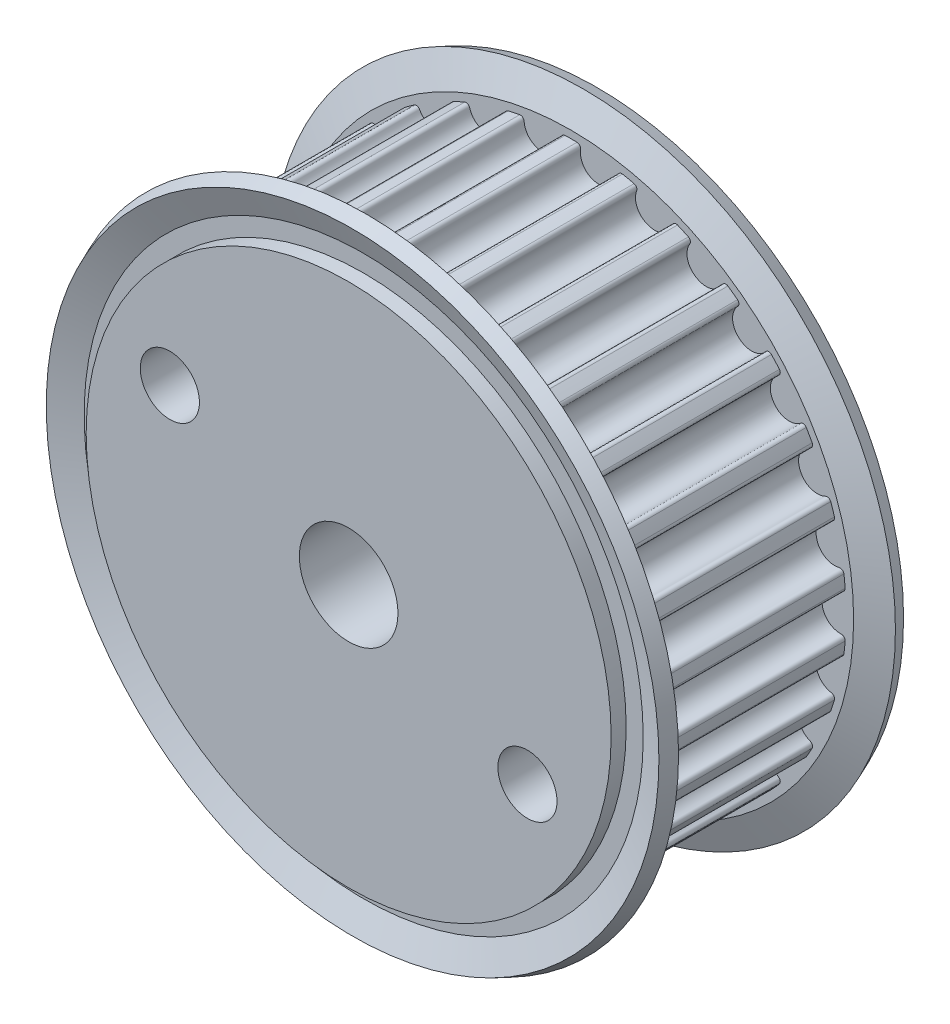
SolidWorks part; units mm, degrees
material "6061 合金"
ref_plane "前视基准面" through (0, 0, 0) normal (0, 0, 1) x (1, 0, 0)
ref_plane "上视基准面" through (0, 0, 0) normal (0, 1, 0) x (1, 0, 0)
ref_plane "右视基准面" through (0, 0, 0) normal (1, 0, 0) x (0, 0, -1)
ref_axis "基准轴1" through (0, 0, 55) along (0, 0, -1)
sketch "SketchRevolveGearBelt01" plane through (0, 0, 0) normal (1, 0, 0) x (0, 0, -1)
  line L0 (0, 0) -> (1, 0) construction
  line L1 (6.4008, 0) -> (6.4008, 13.3069)
  line L2 (6.4008, 13.3069) -> (5.6388, 13.3069)
  line L3 (5.6388, 13.3069) -> (5.6388, 14.1713)
  line L4 (5.6388, 14.1713) -> (6.2015, 15.5299)
  line L5 (6.2015, 15.5299) -> (5.4975, 15.8215)
  line L6 (5.4975, 15.8215) -> (4.8768, 14.3229)
  line L7 (4.8768, 14.3229) -> (4.8768, 13.9419)
  line L8 (4.8768, 13.9419) -> (-4.8768, 13.9419)
  line L9 (-4.8768, 13.9419) -> (-4.8768, 14.3229)
  line L10 (-4.8768, 14.3229) -> (-5.4975, 15.8215)
  line L11 (-5.4975, 15.8215) -> (-6.2015, 15.5299)
  line L12 (-6.2015, 15.5299) -> (-5.6388, 14.1713)
  line L13 (-5.6388, 14.1713) -> (-5.6388, 13.3069)
  line L14 (-5.6388, 13.3069) -> (-6.4008, 13.3069)
  line L15 (-6.4008, 13.3069) -> (-6.4008, 0)
  line L16 (-6.4008, 0) -> (6.4008, 0)
  dimension "GearBeltFlange1OutsideLength" = 0.8644
  dimension "GearBeltFlange1X" = 0.5627
  dimension "GearBeltFlange1Y" = 1.3586
  dimension "GearBeltFlangeThickness" = 0.762
  dimension "GearBeltFlangeInside" = 0.381
  dimension "GearBeltOutsideDiameter" = 13.9419
  dimension "GearBeltFlange2X" = 0.5627
revolve "GearBelt01" add sketch "SketchRevolveGearBelt01" angle 360 about L0
sketch "SketchToothGearBelt01" plane through (0, 0, 0) normal (0, 0, 1) x (1, 0, 0)
  arc A0 (13.8935, 1.162) -> (13.8935, -1.162) centre (0, 0) cw
  spline S0 degree 3 poles (13.8935, -1.162) (13.8944, -1.1516) (13.8944, -1.1357) (13.8918, -1.1148) (13.8886, -1.0994) (13.8841, -1.0843) (13.8784, -1.0695) (13.8714, -1.0553) (13.8634, -1.0418) (13.8542, -1.0289) (13.844, -1.0168) (13.8329, -1.0057) (13.8209, -0.9954) (13.808, -0.9862) (13.7945, -0.9781) (13.7803, -0.9712) (13.7656, -0.9654) (13.7505, -0.9609) (13.735, -0.9576) (13.7194, -0.9556) (13.6903, -0.9547) (13.6423, -0.9556) (13.5752, -0.953) (13.503, -0.9442) (13.4317, -0.9299) (13.3617, -0.91) (13.2935, -0.8847) (13.2275, -0.8541) (13.1641, -0.8184) (13.1036, -0.7779) (13.0466, -0.7328) (12.9932, -0.6834) (12.9439, -0.6299) (12.8989, -0.5727) (12.8585, -0.5122) (12.8231, -0.4487) (12.7926, -0.3826) (12.7675, -0.3143) (12.7478, -0.2443) (12.7336, -0.1729) (12.725, -0.1007) (12.7231, -0.0476) (12.7232, -0.014) (12.7232, 0) (12.7232, 0.014) (12.7231, 0.0476) (12.725, 0.1007) (12.7336, 0.1729) (12.7478, 0.2443) (12.7675, 0.3143) (12.7926, 0.3826) (12.8231, 0.4487) (12.8585, 0.5122) (12.8989, 0.5727) (12.9439, 0.6299) (12.9932, 0.6834) (13.0466, 0.7328) (13.1036, 0.7779) (13.1641, 0.8184) (13.2275, 0.8541) (13.2935, 0.8847) (13.3617, 0.91) (13.4317, 0.9299) (13.503, 0.9442) (13.5752, 0.953) (13.6423, 0.9556) (13.6903, 0.9547) (13.7194, 0.9556) (13.735, 0.9576) (13.7505, 0.9609) (13.7656, 0.9654) (13.7803, 0.9712) (13.7945, 0.9781) (13.808, 0.9862) (13.8209, 0.9954) (13.8329, 1.0057) (13.844, 1.0168) (13.8542, 1.0289) (13.8634, 1.0418) (13.8714, 1.0553) (13.8784, 1.0695) (13.8841, 1.0843) (13.8886, 1.0994) (13.8918, 1.1148) (13.8944, 1.1357) (13.8944, 1.1516) (13.8935, 1.162) knots 0 0 0 0 0.008513 0.012769 0.017025 0.021281 0.025538 0.029794 0.03405 0.038306 0.042563 0.046819 0.051075 0.055331 0.059588 0.063844 0.0681 0.072356 0.076613 0.080869 0.085125 0.100157 0.119771 0.139386 0.159 0.178614 0.198229 0.217843 0.237457 0.257071 0.276686 0.2963 0.315914 0.335529 0.355143 0.374757 0.394372 0.413986 0.4336 0.453214 0.472829 0.492443 0.496222 0.5 0.503778 0.507557 0.527171 0.546786 0.5664 0.586014 0.605628 0.625243 0.644857 0.664471 0.684086 0.7037 0.723314 0.742929 0.762543 0.782157 0.801771 0.821386 0.841 0.860614 0.880229 0.899843 0.914875 0.919131 0.923387 0.927644 0.9319 0.936156 0.940412 0.944669 0.948925 0.953181 0.957437 0.961694 0.96595 0.970206 0.974462 0.978719 0.982975 0.987231 0.991487 1 1 1 1
extrude "ToothExtrudeCutGearBelt01" cut sketch "SketchToothGearBelt01" against normal blind 4.8768 and the other way blind 4.8768
pattern_circular "PatternGearBelt01" count 30 every 12 about axis through (0, 0, 55) along (0, 0, -1) of "ToothExtrudeCutGearBelt01"
sketch "BoreRevolveSketch" plane through (0, 0, 0) normal (1, 0, 0) x (0, 0, -1)
  line L0 (0, 0) -> (1, 0) construction
  line L1 (-6.4008, 0) -> (6.4008, 0)
  line L2 (6.4008, 0) -> (6.4008, 2.5)
  line L3 (6.4008, 2.5) -> (-6.4008, 2.5)
  line L4 (-6.4008, 2.5) -> (-6.4008, 0)
  dimension "TaperSide1" = 2.5
  dimension "TaperSide2" = 2.5
revolve "BoreRevolveCut" cut sketch "BoreRevolveSketch" angle 360 about L0
sketch "AuxiliarySketchGearBelt01" plane through (0, 0, 0) normal (0, 0, 1) x (1, 0, 0)
  circle A0 centre (0, 0) radius 14.3229 construction
  dimension "PitchDiameter" = 28.6458
sketch "草图1" plane through (0, 0, -6.4008) normal (0, 0, -1) x (-1, 0, 0)
  circle A0 centre (-9.0638, -4.2247) radius 1.5
  circle A1 centre (9.0638, 4.2247) radius 1.5
extrude "切除-拉伸1" cut sketch "草图1" against normal blind 17
